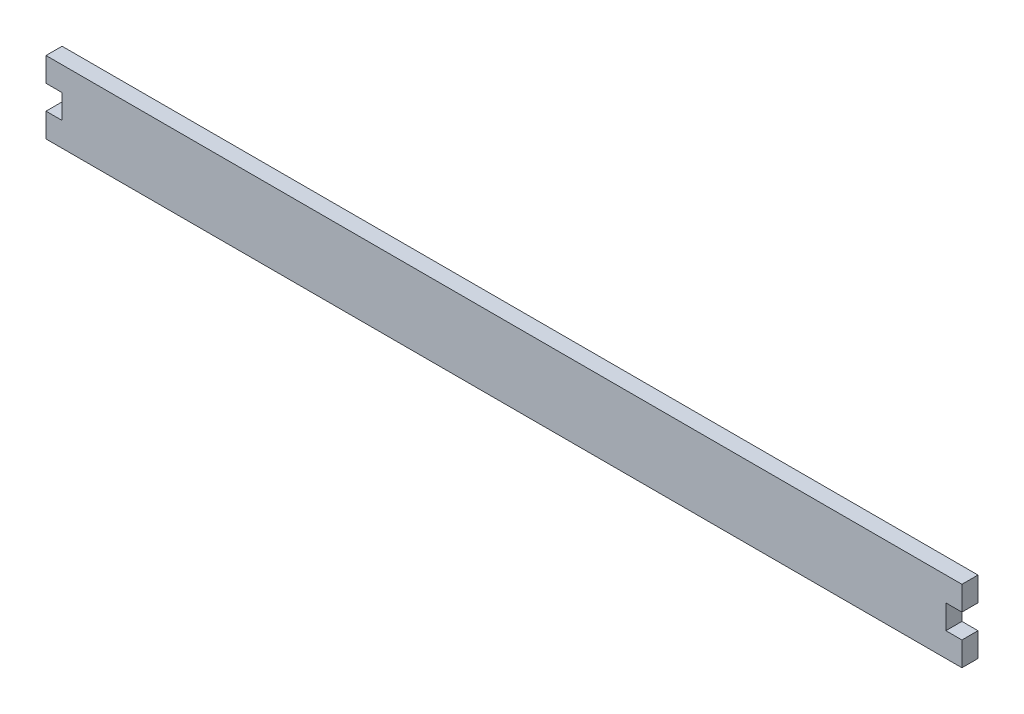
SolidWorks part; units mm, degrees
material "Teak"
ref_plane "Front Plane" through (0, 0, 0) normal (0, 0, 1) x (1, 0, 0)
ref_plane "Top Plane" through (0, 0, 0) normal (0, 1, 0) x (1, 0, 0)
ref_plane "Right Plane" through (0, 0, 0) normal (1, 0, 0) x (0, 0, -1)
sketch "Sketch1" plane through (0, 0, 0) normal (0, 0, 1) x (1, 0, 0)
  line L1 (-285, 22.5) -> (285, 22.5)
  line L2 (-285, 22.5) -> (-285, -22.5)
  line L3 (-285, -22.5) -> (285, -22.5)
  line L4 (285, 22.5) -> (285, -22.5)
  line L5 (-285, 22.5) -> (285, -22.5) construction
  line L6 (-285, -22.5) -> (285, 22.5) construction
  point P0 (0, 0)
  dimension "D1" = 570
  dimension "D2" = 45
extrude "Основа" add sketch "Sketch1" along normal blind 10
sketch "Sketch2" plane through (0, 0, 10) normal (0, 0, 1) x (1, 0, 0)
  line L0 (-285, -7.5) -> (-275, -7.5)
  line L1 (-285, 22.5) -> (-285, -22.5) construction
  line L2 (-275, -7.5) -> (-275, 7.5)
  line L3 (-275, 7.5) -> (-285, 7.5)
  line L4 (-285, 7.5) -> (-285, -7.5)
  line L5 (0, 22.5) -> (0, -22.5) construction
  line L6 (285, 22.5) -> (-285, 22.5) construction
  line L7 (-285, -22.5) -> (285, -22.5) construction
  point P13 (-285, 0)
  point P14 (-285, 0)
  dimension "D1" = 10
  dimension "D2" = 15
extrude "Шип" cut sketch "Sketch2" against normal up to next
sketch "Sketch3" plane through (0, 0, 10) normal (0, 0, 1) x (1, 0, 0)
  line L0 (-275, 7.5) -> (-285, 7.5) construction
  line L1 (-285, 22.5) -> (-285, 7.5) construction
  line L2 (-285, -7.5) -> (-285, -22.5) construction
  circle A0 centre (-280, 15) radius 1.75
  circle A1 centre (-280, -15) radius 1.75
  point P7 (-280, 7.5)
  point P12 (-285, 15)
  point P16 (-285, -15)
  dimension "D1" = 3.5
extrude "Крепежные" [suppressed] cut sketch "Sketch3" against normal up to next
mirror "Mirror1" about plane through (0, 0, 0) normal (1, 0, 0) of "Крепежные", "Шип"
